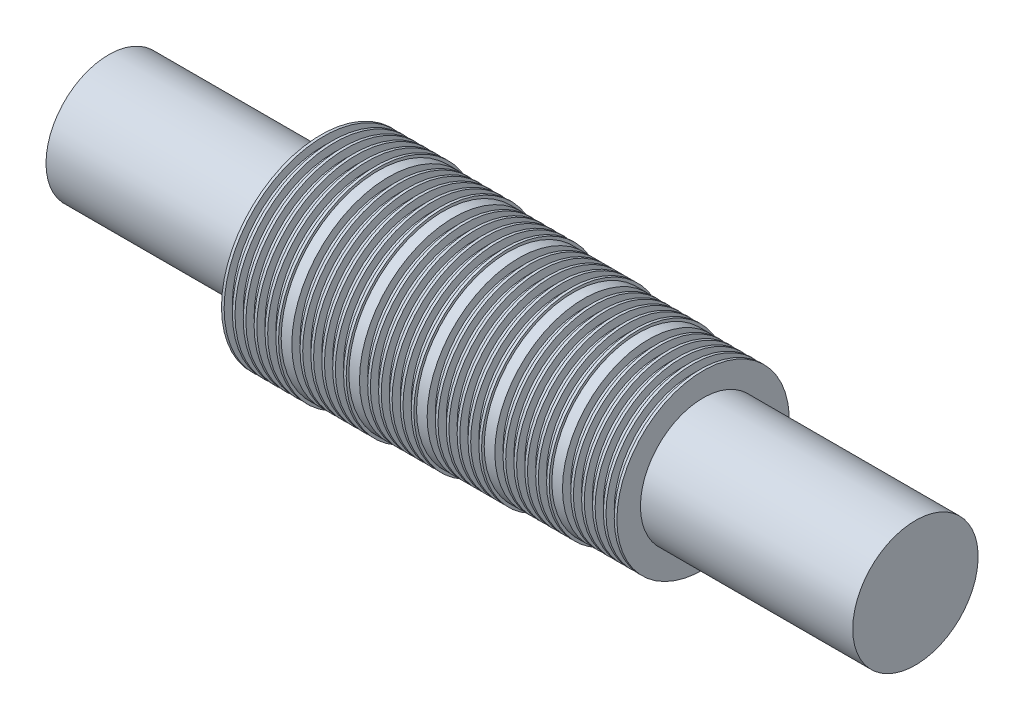
SolidWorks part; units mm, degrees
ref_plane "Front Plane" through (0, 0, 0) normal (0, 0, 1) x (1, 0, 0)
ref_plane "Top Plane" through (0, 0, 0) normal (0, 1, 0) x (1, 0, 0)
ref_plane "Right Plane" through (0, 0, 0) normal (1, 0, 0) x (0, 0, -1)
sketch "Sketch1" plane through (0, 0, 0) normal (0, 0, 1) x (1, 0, 0)
  line L24 (20.574, 9.525) -> (20.574, 8.7376)
  line L25 (20.574, 8.7376) -> (21.3614, 8.7376)
  line L26 (21.3614, 8.7376) -> (21.3614, 9.525)
  line L27 (21.3614, 9.525) -> (21.6154, 9.525)
  line L28 (21.6154, 9.525) -> (21.6154, 8.7376)
  line L29 (21.6154, 8.7376) -> (22.4028, 8.7376)
  line L30 (22.4028, 8.7376) -> (22.4028, 9.525)
  line L31 (22.4028, 9.525) -> (22.6568, 9.525)
  line L32 (22.6568, 9.525) -> (22.6568, 8.7376)
  line L33 (22.6568, 8.7376) -> (23.4442, 8.7376)
  line L34 (23.4442, 8.7376) -> (23.4442, 9.525)
  line L35 (23.4442, 9.525) -> (23.6982, 9.525)
  line L36 (23.6982, 9.525) -> (23.6982, 8.7376)
  line L37 (23.6982, 8.7376) -> (24.4856, 8.7376)
  line L38 (24.4856, 8.7376) -> (24.4856, 9.525)
  line L39 (24.4856, 9.525) -> (24.7396, 9.525)
  line L40 (24.7396, 9.525) -> (24.7396, 8.7376)
  line L41 (24.7396, 8.7376) -> (25.527, 8.7376)
  line L42 (25.527, 8.7376) -> (25.527, 9.525)
  line L43 (25.527, 9.525) -> (25.781, 9.525)
  line L44 (25.781, 9.525) -> (25.781, 9.271)
  line L45 (25.781, 9.271) -> (26.797, 9.271)
  line L46 (26.797, 9.271) -> (26.797, 8.4836)
  line L47 (26.797, 8.4836) -> (27.5844, 8.4836)
  line L48 (27.5844, 8.4836) -> (27.5844, 9.271)
  line L49 (27.5844, 9.271) -> (27.8384, 9.271)
  line L50 (27.8384, 9.271) -> (27.8384, 8.4836)
  line L51 (27.8384, 8.4836) -> (28.6258, 8.4836)
  line L52 (28.6258, 8.4836) -> (28.6258, 9.271)
  line L53 (28.6258, 9.271) -> (28.8798, 9.271)
  line L54 (28.8798, 9.271) -> (28.8798, 8.4836)
  line L55 (28.8798, 8.4836) -> (29.6672, 8.4836)
  line L56 (29.6672, 8.4836) -> (29.6672, 9.271)
  line L57 (29.6672, 9.271) -> (29.9212, 9.271)
  line L58 (29.9212, 9.271) -> (29.9212, 8.4836)
  line L59 (29.9212, 8.4836) -> (30.7086, 8.4836)
  line L60 (30.7086, 8.4836) -> (30.7086, 9.271)
  line L61 (30.7086, 9.271) -> (30.9626, 9.271)
  line L62 (30.9626, 9.271) -> (30.9626, 8.4836)
  line L63 (30.9626, 8.4836) -> (31.75, 8.4836)
  line L64 (31.75, 8.4836) -> (31.75, 9.271)
  line L65 (31.75, 9.271) -> (32.004, 9.271)
  line L66 (32.004, 9.271) -> (32.004, 9.017)
  line L67 (32.004, 9.017) -> (33.02, 9.017)
  line L68 (33.02, 9.017) -> (33.02, 8.2296)
  line L69 (33.02, 8.2296) -> (33.8074, 8.2296)
  line L70 (33.8074, 8.2296) -> (33.8074, 9.017)
  line L71 (33.8074, 9.017) -> (34.0614, 9.017)
  line L72 (34.0614, 9.017) -> (34.0614, 8.2296)
  line L73 (34.0614, 8.2296) -> (34.8488, 8.2296)
  line L74 (34.8488, 8.2296) -> (34.8488, 9.017)
  line L75 (34.8488, 9.017) -> (35.1028, 9.017)
  line L76 (35.1028, 9.017) -> (35.1028, 8.2296)
  line L77 (35.1028, 8.2296) -> (35.8902, 8.2296)
  line L78 (35.8902, 8.2296) -> (35.8902, 9.017)
  line L79 (35.8902, 9.017) -> (36.1442, 9.017)
  line L80 (36.1442, 9.017) -> (36.1442, 8.2296)
  line L81 (36.1442, 8.2296) -> (36.9316, 8.2296)
  line L82 (36.9316, 8.2296) -> (36.9316, 9.017)
  line L83 (36.9316, 9.017) -> (37.1856, 9.017)
  line L84 (37.1856, 9.017) -> (37.1856, 8.2296)
  line L85 (37.1856, 8.2296) -> (37.973, 8.2296)
  line L86 (37.973, 8.2296) -> (37.973, 9.017)
  line L87 (37.973, 9.017) -> (38.227, 9.017)
  line L88 (38.227, 9.017) -> (38.227, 8.763)
  line L89 (38.227, 8.763) -> (39.243, 8.763)
  line L90 (39.243, 8.763) -> (39.243, 7.9756)
  line L91 (39.243, 7.9756) -> (40.0304, 7.9756)
  line L92 (40.0304, 7.9756) -> (40.0304, 8.763)
  line L93 (40.0304, 8.763) -> (40.2844, 8.763)
  line L94 (40.2844, 8.763) -> (40.2844, 7.9756)
  line L95 (40.2844, 7.9756) -> (41.0718, 7.9756)
  line L96 (41.0718, 7.9756) -> (41.0718, 8.763)
  line L97 (41.0718, 8.763) -> (41.3258, 8.763)
  line L98 (41.3258, 8.763) -> (41.3258, 7.9756)
  line L99 (41.3258, 7.9756) -> (42.1132, 7.9756)
  line L100 (42.1132, 7.9756) -> (42.1132, 8.763)
  line L101 (42.1132, 8.763) -> (42.3672, 8.763)
  line L102 (42.3672, 8.763) -> (42.3672, 7.9756)
  line L103 (42.3672, 7.9756) -> (43.1546, 7.9756)
  line L104 (43.1546, 7.9756) -> (43.1546, 8.763)
  line L105 (43.1546, 8.763) -> (43.4086, 8.763)
  line L106 (43.4086, 8.763) -> (43.4086, 7.9756)
  line L107 (43.4086, 7.9756) -> (44.196, 7.9756)
  line L108 (44.196, 7.9756) -> (44.196, 8.763)
  line L109 (44.196, 8.763) -> (44.45, 8.763)
  line L110 (44.45, 8.763) -> (44.45, 8.509)
  line L111 (44.45, 8.509) -> (45.466, 8.509)
  line L112 (45.466, 8.509) -> (45.466, 7.7216)
  line L113 (45.466, 7.7216) -> (46.2534, 7.7216)
  line L114 (46.2534, 7.7216) -> (46.2534, 8.509)
  line L115 (46.2534, 8.509) -> (46.5074, 8.509)
  line L116 (46.5074, 8.509) -> (46.5074, 7.7216)
  line L117 (46.5074, 7.7216) -> (47.2948, 7.7216)
  line L118 (47.2948, 7.7216) -> (47.2948, 8.509)
  line L119 (47.2948, 8.509) -> (47.5488, 8.509)
  line L120 (47.5488, 8.509) -> (47.5488, 7.7216)
  line L121 (47.5488, 7.7216) -> (48.3362, 7.7216)
  line L122 (48.3362, 7.7216) -> (48.3362, 8.509)
  line L123 (48.3362, 8.509) -> (48.5902, 8.509)
  line L124 (48.5902, 8.509) -> (48.5902, 7.7216)
  line L125 (48.5902, 7.7216) -> (49.3776, 7.7216)
  line L126 (49.3776, 7.7216) -> (49.3776, 8.509)
  line L127 (49.3776, 8.509) -> (49.6316, 8.509)
  line L128 (49.6316, 8.509) -> (49.6316, 7.7216)
  line L129 (49.6316, 7.7216) -> (50.419, 7.7216)
  line L130 (50.419, 7.7216) -> (50.419, 8.509)
  line L131 (50.419, 8.509) -> (50.673, 8.509)
  line L132 (50.673, 8.509) -> (50.673, 8.255)
  line L133 (50.673, 8.255) -> (51.689, 8.255)
  line L134 (51.689, 8.255) -> (51.689, 7.4676)
  line L135 (51.689, 7.4676) -> (52.4764, 7.4676)
  line L136 (52.4764, 7.4676) -> (52.4764, 8.255)
  line L137 (52.4764, 8.255) -> (52.7304, 8.255)
  line L138 (52.7304, 8.255) -> (52.7304, 7.4676)
  line L139 (52.7304, 7.4676) -> (53.5178, 7.4676)
  line L140 (53.5178, 7.4676) -> (53.5178, 8.255)
  line L141 (53.5178, 8.255) -> (53.7718, 8.255)
  line L142 (53.7718, 8.255) -> (53.7718, 7.4676)
  line L143 (53.7718, 7.4676) -> (54.5592, 7.4676)
  line L144 (54.5592, 7.4676) -> (54.5592, 8.255)
  line L145 (54.5592, 8.255) -> (54.8132, 8.255)
  line L146 (54.8132, 8.255) -> (54.8132, 7.4676)
  line L147 (54.8132, 7.4676) -> (55.6006, 7.4676)
  line L148 (55.6006, 7.4676) -> (55.6006, 8.255)
  line L149 (55.6006, 8.255) -> (55.8546, 8.255)
  line L150 (55.8546, 8.255) -> (55.8546, 7.4676)
  line L151 (55.8546, 7.4676) -> (56.642, 7.4676)
  line L152 (56.642, 7.4676) -> (56.642, 8.255)
  line L153 (56.642, 8.255) -> (56.896, 8.255)
  line L156 (20.32, 6) -> (0, 6)
  line L157 (0, 6) -> (0, 0)
  line L158 (0, 0) -> (61.976, 0)
  line L160 (20.574, 9.525) -> (20.32, 9.525)
  line L161 (20.32, 9.525) -> (20.32, 6)
  line L162 (56.896, 6) -> (77.216, 6)
  line L163 (77.216, 6) -> (77.216, 0)
  line L164 (77.216, 0) -> (61.976, 0)
  line L165 (56.896, 8.255) -> (56.896, 6)
  point P5 (20.447, 9.525)
  point P6 (67.056, 6)
  dimension "D1" = 6
  dimension "D9" = 20.32
  dimension "D3" = 0.254
  dimension "D4" = 0.7874
  dimension "D5" = 0.7874
  dimension "D7" = 1.016
  dimension "D10" = 6
  dimension "D11" = 20.32
  dimension "D2" = 9.525
  dimension "D6" = 0.254
revolve "Revolve1" add sketch "Sketch1" angle 360 about L158
equation "\"kero_radius\"=0.23622in"
equation "\"D1@Sketch1\"=\"kero_radius\""
equation "\"lox_radius\"=0.23622in"
equation "\"Cavity_width\"=0.031in"
equation "\"tooth_width\"=0.01in"
equation "\"cavity_depth\"=0.031in"
equation "\"seal_step\"=0.01in"
equation "\"purge_length\"=0.04in"
equation "\"D3@Sketch1\"=\"tooth_width\""
equation "\"D4@Sketch1\"=\"Cavity_width\""
equation "\"D5@Sketch1\"=\"cavity_depth\""
equation "\"D7@Sketch1\"=\"purge_length\""
equation "\"D10@Sketch1\"=\"lox_radius\""
equation "\"lox_in_radius\"=.375in"
equation "\"bearing_radius\"= 0.629921"
equation "\"bearing_width\"=0.393701"
equation "\"insert_radius\" = 0.7in"
equation "\"recycle_groove width\" = 0.06in"
equation "\"recycle_groove_depth\" = 0.06in"
equation "\"N2_purge_width\"= .06in"
equation "\"N2_purge_depth\"= .06in"
equation "\"drain_width\"= .06in"
equation "\"drain_depth\"= .06in"
equation "\"radial_clearance\"= .002in"
equation "\"IPS_flange_width\"= .2in"
equation "\"IPS_flange_radius\" = 2.2in"
equation "\"IPS_LOX_male_radius\"= .9in"
equation "\"IPS_Kero_male_radius\" = .9in"
equation "\"IPS_radius\"= 1.5in"
equation "\"InsertLength\"= 1.47in"
equation "\"D2@Sketch1\"=\"lox_in_radius\""
equation "\"D6@Sketch1\"=\"seal_step\""
